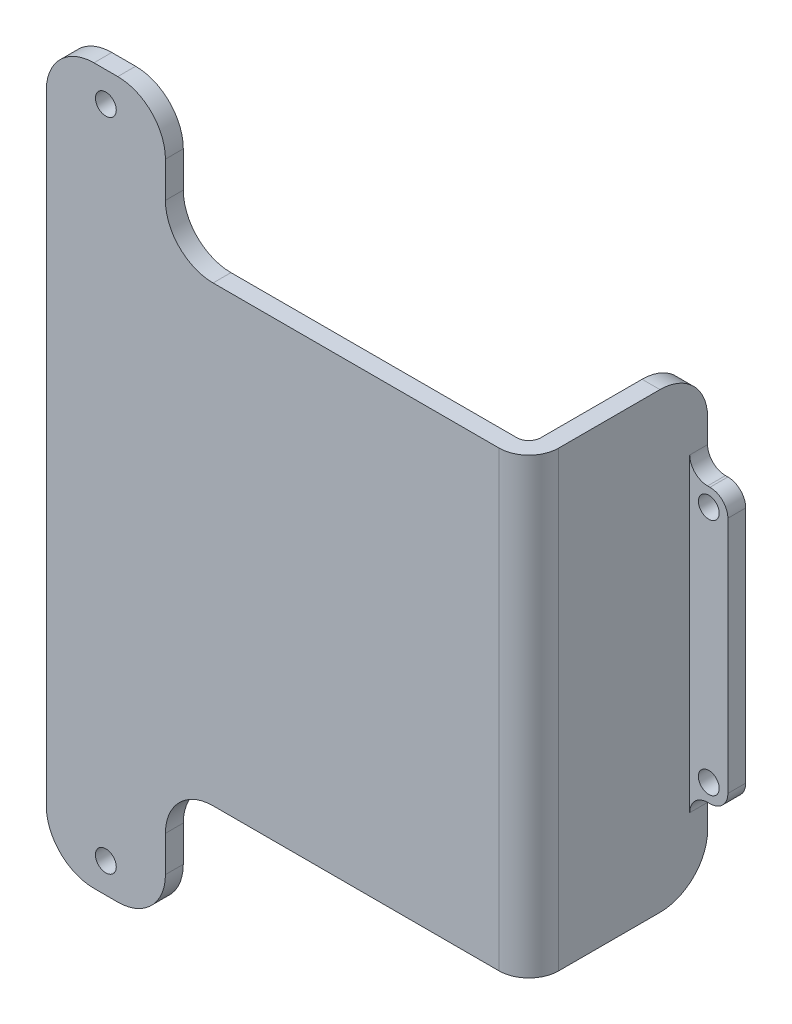
SolidWorks part; units mm, degrees
ref_plane "Plan de face" through (0, 0, 0) normal (0, 0, 1) x (1, 0, 0)
ref_plane "Plan de dessus" through (0, 0, 0) normal (0, 1, 0) x (1, 0, 0)
ref_plane "Plan de droite" through (0, 0, 0) normal (1, 0, 0) x (0, 0, -1)
sketch "Esquisse1" plane through (0, 0, 0) normal (0, 0, 1) x (1, 0, 0)
  line L0 (36.9, 23) -> (30.5, 23)
  line L1 (-30.5, 38) -> (30.5, 38)
  line L2 (-30.5, 38) -> (-30.5, -38)
  line L3 (-30.5, -38) -> (30.5, -38)
  line L4 (30.5, 38) -> (30.5, -38)
  line L5 (-50.5, 60) -> (-50.5, -60)
  line L6 (-50.5, 60) -> (-30.5, 60)
  line L7 (-30.5, 60) -> (-30.5, 38)
  line L8 (36.9, 23) -> (36.9, -23)
  line L9 (-50.5, -60) -> (-30.5, -60)
  line L10 (-30.5, -60) -> (-30.5, -38)
  line L11 (36.9, -23) -> (30.5, -23)
  line L12 (0, 0) -> (30.5, 0) construction
  line L13 (27.5, 38) -> (27.5, -38)
  line L14 (33.7, 20) -> (33.7, 23) construction
  line L15 (30.5, 23) -> (27.5, 23) construction
  circle A1 centre (-40.5, -55) radius 1.75
  circle A3 centre (33.7, 20) radius 1.75
  circle A4 centre (33.7, -20) radius 1.75
  circle A5 centre (-40.5, 55) radius 1.75
  point P4 (0, 38)
  point P6 (-30.5, 0)
  point P20 (33.7, 23)
  point P21 (-50.5, 0)
  point P24 (-40.5, -60)
  point P25 (36.9, 0)
  dimension "D5" = 110
  dimension "D4" = 3.5
  dimension "D1" = 61
  dimension "D2" = 20
  dimension "D3" = 6.4
  dimension "D6" = 40
  dimension "D7" = 5
  dimension "D8" = 76
  dimension "D10" = 3
extrude "Boss.-Extru.1" add sketch "Esquisse1" along normal blind 3 contours L9 L10 L2 L7 L6 L5 A1 A5 | L4 L1 L2 L3 | L13 L1 L2 L3 region at (29, 0, 0) region at (-1.5, 0, 0) region at (-40.5, 0, 0)
extrude "Boss.-Extru.2" add sketch "Esquisse1<3>" against normal blind 27 contours L1 L13 L3 L4 | L11 L8 L0 L4 A3 A4 region at (33.7, 0, 0) region at (29, 0, 0)
sketch "Esquisse1<3>" plane through (0, 0, 0) normal (0, 0, 1) x (1, 0, 0) same geometry as "Esquisse1"
extrude "Enlèv. mat.-Extru.1" cut sketch "Esquisse1<4>" against normal blind 24 contours L11 L8 L0 L4 A3 A4 region at (33.7, 0, 0)
sketch "Esquisse1<4>" plane through (0, 0, 0) normal (0, 0, 1) x (1, 0, 0) same geometry as "Esquisse1"
fillet "Congé1" radius 8 8 edges at (-30.5, 38, 1.5) (-30.5, 60, 1.5) (-50.5, 60, 1.5) (-30.5, -38, 1.5) (-50.5, -60, 1.5) (-30.5, -60, 1.5) (29, 38, -27) (29, -38, -27)
fillet "Congé2" radius 3 4 edges at (30.5, 23, -25.5) (36.9, 23, -25.5) (36.9, -23, -25.5) (30.5, -23, -25.5)
fillet "Congé3" radius 2 1 edges at (27.5, 0, 0)
fillet "Congé4" radius 5 1 edges at (30.5, 0, 3)
